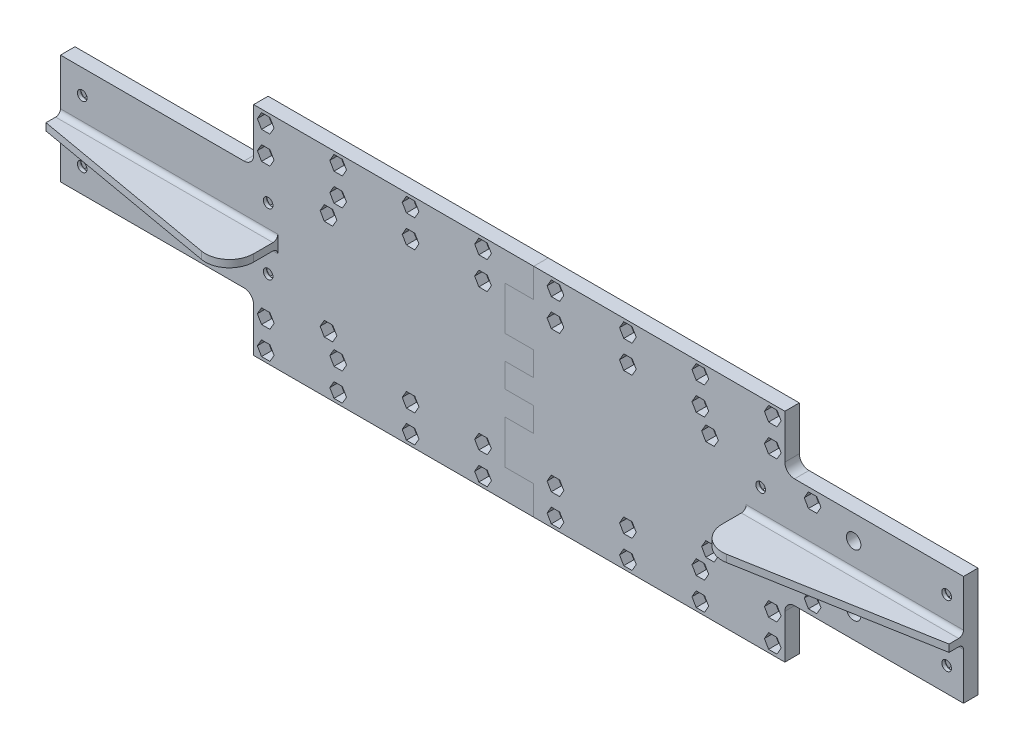
SolidWorks part; units mm, degrees
ref_plane "Top Plane" through (0, 0, 0) normal (0, 0, 1) x (1, 0, 0)
ref_plane "Right Plane" through (0, 0, 0) normal (0, 1, 0) x (1, 0, 0)
ref_plane "Front Plane" through (0, 0, 0) normal (1, 0, 0) x (0, 0, -1)
sketch "Sketch1" plane through (0, 0, 0) normal (0, 0, 1) x (1, 0, 0)
  line L0 (-187, 81) -> (187, -81) construction
  line L1 (-187, 81) -> (187, 81) construction
  line L2 (-187, 81) -> (-187, -81) construction
  line L3 (-187, -81) -> (187, -81) construction
  line L4 (187, 81) -> (187, -81) construction
  line L5 (-187, -22.75) -> (-107, -22.75) construction
  line L6 (-107, -22.75) -> (-107, -81) construction
  line L7 (113, -81) -> (113, -22.75) construction
  line L8 (113, -22.75) -> (187, -22.75) construction
  line L9 (-187, 0) -> (187, 0) construction
  line L10 (113, 22.75) -> (187, 22.75) construction
  line L11 (113, 81) -> (113, 22.75) construction
  line L12 (-107, 22.75) -> (-107, 81) construction
  line L13 (-187, 22.75) -> (-107, 22.75) construction
  line L14 (85.2, -81) -> (85.2, 81) construction
  line L15 (-93, -81) -> (-93, 81) construction
  line L16 (-187, -2.75) -> (187, -2.75) construction
  line L17 (187, 2.75) -> (-187, 2.75) construction
  text T0 "FRONT" font "Century Gothic" height in points 80
  dimension "D1" = 374
  dimension "D2" = 162
  dimension "D3" = 45.5
  dimension "D4" = 80
  dimension "D5" = 74
  dimension "D6" = 27.8
  dimension "D7" = 14
  dimension "D8" = 20
  dimension "D9" = 20
sketch "Sketch2" plane through (0, 0, 0) normal (0, 0, 1) x (1, 0, 0)
  line L0 (-187, 81) -> (-187, -81) construction
  line L1 (-187, 81) -> (187, 81) construction
  line L2 (187, 81) -> (187, -81) construction
  line L3 (-187, -81) -> (187, -81) construction
  line L4 (113, -81) -> (113, -22.75) construction
  line L5 (113, -22.75) -> (187, -22.75) construction
  line L6 (113, 22.75) -> (187, 22.75) construction
  line L7 (113, 81) -> (113, 22.75) construction
  line L8 (-107, 22.75) -> (-107, 81) construction
  line L9 (-187, 22.75) -> (-107, 22.75) construction
  line L10 (-107, -22.75) -> (-107, -81) construction
  line L11 (-187, -22.75) -> (-107, -22.75) construction
  line L12 (-187, 22.75) -> (-187, -22.75)
  line L13 (-107, 81) -> (113, 81)
  line L14 (187, 22.75) -> (187, -22.75)
  line L15 (-107, -81) -> (113, -81)
  line L16 (113, -81) -> (113, -22.75)
  line L17 (113, -22.75) -> (187, -22.75)
  line L18 (113, 22.75) -> (187, 22.75)
  line L19 (113, 81) -> (113, 22.75)
  line L20 (-107, 22.75) -> (-107, 81)
  line L21 (-187, 22.75) -> (-107, 22.75)
  line L22 (-107, -22.75) -> (-107, -81)
  line L23 (-187, -22.75) -> (-107, -22.75)
extrude "Boss-Extrude1" add sketch "Sketch2" along normal mid plane 6
sketch "Sketch5" plane through (0, 0, -3) normal (0, 0, -1) x (-1, 0, 0)
  line L0 (0, 81) -> (0, -81) construction
  line L1 (187, 81) -> (-187, 81) construction
  line L2 (187, -81) -> (-187, -81) construction
  line L4 (-180, 0) -> (178, 0) construction
  line L5 (-180, 12.75) -> (-103, 12.75) construction
  line L6 (-180, 12.75) -> (-180, -12.75) construction
  line L7 (-180, -12.75) -> (-103, -12.75) construction
  line L8 (-103, 12.75) -> (-103, -12.75) construction
  line L9 (101, 12.75) -> (178, 12.75) construction
  line L10 (101, 12.75) -> (101, -12.75) construction
  line L11 (101, -12.75) -> (178, -12.75) construction
  line L12 (178, 12.75) -> (178, -12.75) construction
  circle A8 centre (-103, -12.75) radius 2
  circle A9 centre (-103, 12.75) radius 2
  circle A10 centre (-180, 12.75) radius 2
  circle A11 centre (-180, -12.75) radius 2
  circle A12 centre (178, 12.75) radius 2
  circle A13 centre (178, -12.75) radius 2
  circle A14 centre (101, -12.75) radius 2
  circle A15 centre (101, 12.75) radius 2
  dimension "D3" = 25.5
  dimension "D6" = 4
  dimension "D1" = 77
  dimension "D2" = 103
  dimension "D4" = 101
  dimension "D5" = 77
extrude "Cut-Extrude2" cut sketch "Sketch5" against normal up to next
sketch "Sketch9" plane through (0, 0, 3) normal (0, 0, 1) x (1, 0, 0)
  line L0 (-107.9535, -35) -> (101.269, -35) construction
  line L1 (-12, -40.75) -> (18, -40.75) construction
  line L2 (-12, -29.25) -> (-42, -29.25) construction
  line L3 (-12, -29.25) -> (18, -29.25) construction
  line L4 (-194.5845, 0) -> (205.1662, 0) construction
  line L5 (3, -85.4344) -> (3, 85.4344) construction
  line L6 (-12, -40.75) -> (-42, -40.75) construction
  line L7 (-107, 81) -> (113, -81) construction
  line L8 (-40.2679, -37.75) -> (-43.7321, -37.75) construction
  line L9 (-13.7321, -37.75) -> (-15.4641, -40.75) construction
  line L10 (-15.4641, -40.75) -> (-13.7321, -43.75) construction
  line L11 (-13.7321, -43.75) -> (-10.2679, -43.75) construction
  line L12 (-10.2679, -43.75) -> (-8.5359, -40.75) construction
  line L13 (-8.5359, -40.75) -> (-10.2679, -37.75) construction
  line L14 (-10.2679, -37.75) -> (-13.7321, -37.75) construction
  line L15 (-43.7321, -37.75) -> (-45.4641, -40.75) construction
  line L16 (-45.4641, -40.75) -> (-43.7321, -43.75) construction
  line L17 (-43.7321, -43.75) -> (-40.2679, -43.75) construction
  line L18 (-40.2679, -43.75) -> (-38.5359, -40.75) construction
  line L19 (-38.5359, -40.75) -> (-40.2679, -37.75) construction
  line L20 (-70.2679, -37.75) -> (-73.7321, -37.75) construction
  line L21 (-73.7321, -37.75) -> (-75.4641, -40.75) construction
  line L22 (-75.4641, -40.75) -> (-73.7321, -43.75) construction
  line L23 (-73.7321, -43.75) -> (-70.2679, -43.75) construction
  line L24 (-70.2679, -43.75) -> (-68.5359, -40.75) construction
  line L25 (-68.5359, -40.75) -> (-70.2679, -37.75) construction
  line L26 (-100.2679, -37.75) -> (-103.7321, -37.75) construction
  line L27 (-103.7321, -37.75) -> (-105.4641, -40.75) construction
  line L28 (-105.4641, -40.75) -> (-103.7321, -43.75) construction
  line L29 (-103.7321, -43.75) -> (-100.2679, -43.75) construction
  line L30 (-100.2679, -43.75) -> (-98.5359, -40.75) construction
  line L31 (-98.5359, -40.75) -> (-100.2679, -37.75) construction
  line L32 (-43.7321, -37.75) -> (-40.2679, -43.75) construction
  line L33 (-42, -40.75) -> (-12, -40.75) construction
  line L34 (-8.5359, -29.25) -> (-10.2679, -32.25) construction
  line L35 (-10.2679, -26.25) -> (-8.5359, -29.25) construction
  line L36 (-13.7321, -26.25) -> (-10.2679, -26.25) construction
  line L37 (-15.4641, -29.25) -> (-13.7321, -26.25) construction
  line L38 (-13.7321, -32.25) -> (-15.4641, -29.25) construction
  line L39 (-10.2679, -32.25) -> (-13.7321, -32.25) construction
  line L40 (-43.7321, -26.25) -> (-40.2679, -26.25) construction
  line L41 (-45.4641, -29.25) -> (-43.7321, -26.25) construction
  line L42 (-43.7321, -32.25) -> (-45.4641, -29.25) construction
  line L43 (-40.2679, -32.25) -> (-43.7321, -32.25) construction
  line L44 (-38.5359, -29.25) -> (-40.2679, -32.25) construction
  line L45 (-40.2679, -26.25) -> (-38.5359, -29.25) construction
  line L46 (-73.7321, -26.25) -> (-70.2679, -26.25) construction
  line L47 (-75.4641, -29.25) -> (-73.7321, -26.25) construction
  line L48 (-73.7321, -32.25) -> (-75.4641, -29.25) construction
  line L49 (-70.2679, -32.25) -> (-73.7321, -32.25) construction
  line L50 (-68.5359, -29.25) -> (-70.2679, -32.25) construction
  line L51 (-70.2679, -26.25) -> (-68.5359, -29.25) construction
  line L52 (-103.7321, -26.25) -> (-100.2679, -26.25) construction
  line L53 (-105.4641, -29.25) -> (-103.7321, -26.25) construction
  line L54 (-103.7321, -32.25) -> (-105.4641, -29.25) construction
  line L55 (-100.2679, -32.25) -> (-103.7321, -32.25) construction
  line L56 (-98.5359, -29.25) -> (-100.2679, -32.25) construction
  line L57 (-100.2679, -26.25) -> (-98.5359, -29.25) construction
  line L58 (106.2679, -26.25) -> (104.5359, -29.25) construction
  line L59 (104.5359, -29.25) -> (106.2679, -32.25) construction
  line L60 (106.2679, -32.25) -> (109.7321, -32.25) construction
  line L61 (109.7321, -32.25) -> (111.4641, -29.25) construction
  line L62 (111.4641, -29.25) -> (109.7321, -26.25) construction
  line L63 (109.7321, -26.25) -> (106.2679, -26.25) construction
  line L64 (76.2679, -26.25) -> (74.5359, -29.25) construction
  line L65 (74.5359, -29.25) -> (76.2679, -32.25) construction
  line L66 (76.2679, -32.25) -> (79.7321, -32.25) construction
  line L67 (79.7321, -32.25) -> (81.4641, -29.25) construction
  line L68 (81.4641, -29.25) -> (79.7321, -26.25) construction
  line L69 (79.7321, -26.25) -> (76.2679, -26.25) construction
  line L70 (46.2679, -26.25) -> (44.5359, -29.25) construction
  line L71 (44.5359, -29.25) -> (46.2679, -32.25) construction
  line L72 (46.2679, -32.25) -> (49.7321, -32.25) construction
  line L73 (49.7321, -32.25) -> (51.4641, -29.25) construction
  line L74 (51.4641, -29.25) -> (49.7321, -26.25) construction
  line L75 (49.7321, -26.25) -> (46.2679, -26.25) construction
  line L76 (16.2679, -32.25) -> (19.7321, -32.25) construction
  line L77 (19.7321, -32.25) -> (21.4641, -29.25) construction
  line L78 (21.4641, -29.25) -> (19.7321, -26.25) construction
  line L79 (19.7321, -26.25) -> (16.2679, -26.25) construction
  line L80 (16.2679, -26.25) -> (14.5359, -29.25) construction
  line L81 (14.5359, -29.25) -> (16.2679, -32.25) construction
  line L82 (48, -40.75) -> (18, -40.75) construction
  line L83 (49.7321, -37.75) -> (46.2679, -43.75) construction
  line L84 (104.5359, -40.75) -> (106.2679, -37.75) construction
  line L85 (106.2679, -43.75) -> (104.5359, -40.75) construction
  line L86 (109.7321, -43.75) -> (106.2679, -43.75) construction
  line L87 (111.4641, -40.75) -> (109.7321, -43.75) construction
  line L88 (109.7321, -37.75) -> (111.4641, -40.75) construction
  line L89 (106.2679, -37.75) -> (109.7321, -37.75) construction
  line L90 (74.5359, -40.75) -> (76.2679, -37.75) construction
  line L91 (76.2679, -43.75) -> (74.5359, -40.75) construction
  line L92 (79.7321, -43.75) -> (76.2679, -43.75) construction
  line L93 (81.4641, -40.75) -> (79.7321, -43.75) construction
  line L94 (79.7321, -37.75) -> (81.4641, -40.75) construction
  line L95 (76.2679, -37.75) -> (79.7321, -37.75) construction
  line L96 (44.5359, -40.75) -> (46.2679, -37.75) construction
  line L97 (46.2679, -43.75) -> (44.5359, -40.75) construction
  line L98 (49.7321, -43.75) -> (46.2679, -43.75) construction
  line L99 (51.4641, -40.75) -> (49.7321, -43.75) construction
  line L100 (49.7321, -37.75) -> (51.4641, -40.75) construction
  line L101 (16.2679, -37.75) -> (19.7321, -37.75) construction
  line L102 (14.5359, -40.75) -> (16.2679, -37.75) construction
  line L103 (16.2679, -43.75) -> (14.5359, -40.75) construction
  line L104 (19.7321, -43.75) -> (16.2679, -43.75) construction
  line L105 (21.4641, -40.75) -> (19.7321, -43.75) construction
  line L106 (19.7321, -37.75) -> (21.4641, -40.75) construction
  line L107 (46.2679, -37.75) -> (49.7321, -37.75) construction
  line L108 (46.2679, 37.75) -> (49.7321, 37.75) construction
  line L109 (19.7321, 37.75) -> (21.4641, 40.75) construction
  line L110 (21.4641, 40.75) -> (19.7321, 43.75) construction
  line L111 (19.7321, 43.75) -> (16.2679, 43.75) construction
  line L112 (16.2679, 43.75) -> (14.5359, 40.75) construction
  line L113 (14.5359, 40.75) -> (16.2679, 37.75) construction
  line L114 (16.2679, 37.75) -> (19.7321, 37.75) construction
  line L115 (49.7321, 37.75) -> (51.4641, 40.75) construction
  line L116 (51.4641, 40.75) -> (49.7321, 43.75) construction
  line L117 (49.7321, 43.75) -> (46.2679, 43.75) construction
  line L118 (46.2679, 43.75) -> (44.5359, 40.75) construction
  line L119 (44.5359, 40.75) -> (46.2679, 37.75) construction
  line L120 (76.2679, 37.75) -> (79.7321, 37.75) construction
  line L121 (79.7321, 37.75) -> (81.4641, 40.75) construction
  line L122 (81.4641, 40.75) -> (79.7321, 43.75) construction
  line L123 (79.7321, 43.75) -> (76.2679, 43.75) construction
  line L124 (76.2679, 43.75) -> (74.5359, 40.75) construction
  line L125 (74.5359, 40.75) -> (76.2679, 37.75) construction
  line L126 (106.2679, 37.75) -> (109.7321, 37.75) construction
  line L127 (109.7321, 37.75) -> (111.4641, 40.75) construction
  line L128 (111.4641, 40.75) -> (109.7321, 43.75) construction
  line L129 (109.7321, 43.75) -> (106.2679, 43.75) construction
  line L130 (106.2679, 43.75) -> (104.5359, 40.75) construction
  line L131 (104.5359, 40.75) -> (106.2679, 37.75) construction
  line L132 (49.7321, 37.75) -> (46.2679, 43.75) construction
  line L133 (48, 40.75) -> (18, 40.75) construction
  line L134 (14.5359, 29.25) -> (16.2679, 32.25) construction
  line L135 (16.2679, 26.25) -> (14.5359, 29.25) construction
  line L136 (19.7321, 26.25) -> (16.2679, 26.25) construction
  line L137 (21.4641, 29.25) -> (19.7321, 26.25) construction
  line L138 (19.7321, 32.25) -> (21.4641, 29.25) construction
  line L139 (16.2679, 32.25) -> (19.7321, 32.25) construction
  line L140 (49.7321, 26.25) -> (46.2679, 26.25) construction
  line L141 (51.4641, 29.25) -> (49.7321, 26.25) construction
  line L142 (49.7321, 32.25) -> (51.4641, 29.25) construction
  line L143 (46.2679, 32.25) -> (49.7321, 32.25) construction
  line L144 (44.5359, 29.25) -> (46.2679, 32.25) construction
  line L145 (46.2679, 26.25) -> (44.5359, 29.25) construction
  line L146 (79.7321, 26.25) -> (76.2679, 26.25) construction
  line L147 (81.4641, 29.25) -> (79.7321, 26.25) construction
  line L148 (79.7321, 32.25) -> (81.4641, 29.25) construction
  line L149 (76.2679, 32.25) -> (79.7321, 32.25) construction
  line L150 (74.5359, 29.25) -> (76.2679, 32.25) construction
  line L151 (76.2679, 26.25) -> (74.5359, 29.25) construction
  line L152 (109.7321, 26.25) -> (106.2679, 26.25) construction
  line L153 (111.4641, 29.25) -> (109.7321, 26.25) construction
  line L154 (109.7321, 32.25) -> (111.4641, 29.25) construction
  line L155 (106.2679, 32.25) -> (109.7321, 32.25) construction
  line L156 (104.5359, 29.25) -> (106.2679, 32.25) construction
  line L157 (106.2679, 26.25) -> (104.5359, 29.25) construction
  line L158 (-100.2679, 26.25) -> (-98.5359, 29.25) construction
  line L159 (-98.5359, 29.25) -> (-100.2679, 32.25) construction
  line L160 (-100.2679, 32.25) -> (-103.7321, 32.25) construction
  line L161 (-103.7321, 32.25) -> (-105.4641, 29.25) construction
  line L162 (-105.4641, 29.25) -> (-103.7321, 26.25) construction
  line L163 (-103.7321, 26.25) -> (-100.2679, 26.25) construction
  line L164 (-70.2679, 26.25) -> (-68.5359, 29.25) construction
  line L165 (-68.5359, 29.25) -> (-70.2679, 32.25) construction
  line L166 (-70.2679, 32.25) -> (-73.7321, 32.25) construction
  line L167 (-73.7321, 32.25) -> (-75.4641, 29.25) construction
  line L168 (-75.4641, 29.25) -> (-73.7321, 26.25) construction
  line L169 (-73.7321, 26.25) -> (-70.2679, 26.25) construction
  line L170 (-40.2679, 26.25) -> (-38.5359, 29.25) construction
  line L171 (-38.5359, 29.25) -> (-40.2679, 32.25) construction
  line L172 (-40.2679, 32.25) -> (-43.7321, 32.25) construction
  line L173 (-43.7321, 32.25) -> (-45.4641, 29.25) construction
  line L174 (-45.4641, 29.25) -> (-43.7321, 26.25) construction
  line L175 (-43.7321, 26.25) -> (-40.2679, 26.25) construction
  line L176 (-10.2679, 32.25) -> (-13.7321, 32.25) construction
  line L177 (-13.7321, 32.25) -> (-15.4641, 29.25) construction
  line L178 (-15.4641, 29.25) -> (-13.7321, 26.25) construction
  line L179 (-13.7321, 26.25) -> (-10.2679, 26.25) construction
  line L180 (-10.2679, 26.25) -> (-8.5359, 29.25) construction
  line L181 (-8.5359, 29.25) -> (-10.2679, 32.25) construction
  line L182 (-42, 40.75) -> (-12, 40.75) construction
  line L183 (-43.7321, 37.75) -> (-40.2679, 43.75) construction
  line L184 (-98.5359, 40.75) -> (-100.2679, 37.75) construction
  line L185 (-100.2679, 43.75) -> (-98.5359, 40.75) construction
  line L186 (-103.7321, 43.75) -> (-100.2679, 43.75) construction
  line L187 (-105.4641, 40.75) -> (-103.7321, 43.75) construction
  line L188 (-103.7321, 37.75) -> (-105.4641, 40.75) construction
  line L189 (-100.2679, 37.75) -> (-103.7321, 37.75) construction
  line L190 (-68.5359, 40.75) -> (-70.2679, 37.75) construction
  line L191 (-70.2679, 43.75) -> (-68.5359, 40.75) construction
  line L192 (-73.7321, 43.75) -> (-70.2679, 43.75) construction
  line L193 (-75.4641, 40.75) -> (-73.7321, 43.75) construction
  line L194 (-73.7321, 37.75) -> (-75.4641, 40.75) construction
  line L195 (-70.2679, 37.75) -> (-73.7321, 37.75) construction
  line L196 (-38.5359, 40.75) -> (-40.2679, 37.75) construction
  line L197 (-40.2679, 43.75) -> (-38.5359, 40.75) construction
  line L198 (-43.7321, 43.75) -> (-40.2679, 43.75) construction
  line L199 (-45.4641, 40.75) -> (-43.7321, 43.75) construction
  line L200 (-43.7321, 37.75) -> (-45.4641, 40.75) construction
  line L201 (-10.2679, 37.75) -> (-13.7321, 37.75) construction
  line L202 (-8.5359, 40.75) -> (-10.2679, 37.75) construction
  line L203 (-10.2679, 43.75) -> (-8.5359, 40.75) construction
  line L204 (-13.7321, 43.75) -> (-10.2679, 43.75) construction
  line L205 (-15.4641, 40.75) -> (-13.7321, 43.75) construction
  line L206 (-13.7321, 37.75) -> (-15.4641, 40.75) construction
  line L207 (-40.2679, 37.75) -> (-43.7321, 37.75) construction
  line L208 (-12, 40.75) -> (-42, 40.75) construction
  line L209 (-12, 29.25) -> (18, 29.25) construction
  line L210 (-12, 29.25) -> (-42, 29.25) construction
  line L211 (-12, 40.75) -> (18, 40.75) construction
  line L212 (-107.9535, 35) -> (101.269, 35) construction
  circle A0 centre (-12, -40.75) radius 1.75
  circle A1 centre (-42, -40.75) radius 1.75
  circle A2 centre (-72, -40.75) radius 1.75
  circle A3 centre (-102, -40.75) radius 1.75
  circle A4 centre (108, -40.75) radius 1.75
  circle A5 centre (78, -40.75) radius 1.75
  circle A6 centre (48, -40.75) radius 1.75
  circle A7 centre (18, -40.75) radius 1.75
  circle A8 centre (18, -29.25) radius 1.75
  circle A9 centre (48, -29.25) radius 1.75
  circle A10 centre (78, -29.25) radius 1.75
  circle A11 centre (108, -29.25) radius 1.75
  circle A12 centre (-102, -29.25) radius 1.75
  circle A13 centre (-72, -29.25) radius 1.75
  circle A14 centre (-42, -29.25) radius 1.75
  circle A15 centre (-12, -29.25) radius 1.75
  circle A16 centre (-12, -40.75) radius 3 construction
  circle A17 centre (-12, 40.75) radius 3 construction
  circle A18 centre (-12, 29.25) radius 1.75
  circle A19 centre (-42, 29.25) radius 1.75
  circle A20 centre (-72, 29.25) radius 1.75
  circle A21 centre (-102, 29.25) radius 1.75
  circle A22 centre (108, 29.25) radius 1.75
  circle A23 centre (78, 29.25) radius 1.75
  circle A24 centre (48, 29.25) radius 1.75
  circle A25 centre (18, 29.25) radius 1.75
  circle A26 centre (18, 40.75) radius 1.75
  circle A27 centre (48, 40.75) radius 1.75
  circle A28 centre (78, 40.75) radius 1.75
  circle A29 centre (108, 40.75) radius 1.75
  circle A30 centre (-102, 40.75) radius 1.75
  circle A31 centre (-72, 40.75) radius 1.75
  circle A32 centre (-42, 40.75) radius 1.75
  circle A33 centre (-12, 40.75) radius 1.75
  point P6 (3, -40.75)
  point P39 (3, -29.25)
  point P46 (3, 0)
  point P277 (3, 29.25)
  point P278 (3, 40.75)
  dimension "D3" = 3.5
  dimension "D1" = 11.5
  dimension "D2" = 35
  dimension "D5" = 30
  dimension "D6" = 6
  dimension "D4" = 4
  dimension "D7" = 4
extrude "Cut-Extrude6" cut sketch "Sketch9" against normal through all
sketch "Sketch10" plane through (0, 0, 3) normal (0, 0, 1) x (1, 0, 0)
  line L0 (-103.7321, -43.75) -> (-100.2679, -43.75) construction
  line L1 (-105.4641, -40.75) -> (-103.7321, -43.75) construction
  line L2 (-103.7321, -37.75) -> (-105.4641, -40.75) construction
  line L3 (-100.2679, -37.75) -> (-103.7321, -37.75) construction
  line L4 (-98.5359, -40.75) -> (-100.2679, -37.75) construction
  line L5 (-100.2679, -43.75) -> (-98.5359, -40.75) construction
  line L6 (-103.7321, -43.75) -> (-100.2679, -43.75)
  line L7 (-105.4641, -40.75) -> (-103.7321, -43.75)
  line L8 (-103.7321, -37.75) -> (-105.4641, -40.75)
  line L9 (-100.2679, -37.75) -> (-103.7321, -37.75)
  line L10 (-98.5359, -40.75) -> (-100.2679, -37.75)
  line L11 (-100.2679, -43.75) -> (-98.5359, -40.75)
  line L12 (-73.7321, -43.75) -> (-70.2679, -43.75) construction
  line L13 (-75.4641, -40.75) -> (-73.7321, -43.75) construction
  line L14 (-73.7321, -37.75) -> (-75.4641, -40.75) construction
  line L15 (-70.2679, -37.75) -> (-73.7321, -37.75) construction
  line L16 (-68.5359, -40.75) -> (-70.2679, -37.75) construction
  line L17 (-70.2679, -43.75) -> (-68.5359, -40.75) construction
  line L18 (-73.7321, -43.75) -> (-70.2679, -43.75)
  line L19 (-75.4641, -40.75) -> (-73.7321, -43.75)
  line L20 (-73.7321, -37.75) -> (-75.4641, -40.75)
  line L21 (-70.2679, -37.75) -> (-73.7321, -37.75)
  line L22 (-68.5359, -40.75) -> (-70.2679, -37.75)
  line L23 (-70.2679, -43.75) -> (-68.5359, -40.75)
  line L24 (-43.7321, -43.75) -> (-40.2679, -43.75) construction
  line L25 (-45.4641, -40.75) -> (-43.7321, -43.75) construction
  line L26 (-43.7321, -37.75) -> (-45.4641, -40.75) construction
  line L27 (-40.2679, -37.75) -> (-43.7321, -37.75) construction
  line L28 (-38.5359, -40.75) -> (-40.2679, -37.75) construction
  line L29 (-40.2679, -43.75) -> (-38.5359, -40.75) construction
  line L30 (-43.7321, -43.75) -> (-40.2679, -43.75)
  line L31 (-45.4641, -40.75) -> (-43.7321, -43.75)
  line L32 (-43.7321, -37.75) -> (-45.4641, -40.75)
  line L33 (-40.2679, -37.75) -> (-43.7321, -37.75)
  line L34 (-38.5359, -40.75) -> (-40.2679, -37.75)
  line L35 (-40.2679, -43.75) -> (-38.5359, -40.75)
  line L36 (-13.7321, -43.75) -> (-10.2679, -43.75) construction
  line L37 (-15.4641, -40.75) -> (-13.7321, -43.75) construction
  line L38 (-13.7321, -37.75) -> (-15.4641, -40.75) construction
  line L39 (-10.2679, -37.75) -> (-13.7321, -37.75) construction
  line L40 (-8.5359, -40.75) -> (-10.2679, -37.75) construction
  line L41 (-10.2679, -43.75) -> (-8.5359, -40.75) construction
  line L42 (-13.7321, -43.75) -> (-10.2679, -43.75)
  line L43 (-15.4641, -40.75) -> (-13.7321, -43.75)
  line L44 (-13.7321, -37.75) -> (-15.4641, -40.75)
  line L45 (-10.2679, -37.75) -> (-13.7321, -37.75)
  line L46 (-8.5359, -40.75) -> (-10.2679, -37.75)
  line L47 (-10.2679, -43.75) -> (-8.5359, -40.75)
  line L48 (79.7321, -43.75) -> (76.2679, -43.75) construction
  line L49 (81.4641, -40.75) -> (79.7321, -43.75) construction
  line L50 (79.7321, -37.75) -> (81.4641, -40.75) construction
  line L51 (76.2679, -37.75) -> (79.7321, -37.75) construction
  line L52 (74.5359, -40.75) -> (76.2679, -37.75) construction
  line L53 (76.2679, -43.75) -> (74.5359, -40.75) construction
  line L54 (46.2679, -37.75) -> (49.7321, -37.75) construction
  line L55 (44.5359, -40.75) -> (46.2679, -37.75) construction
  line L56 (46.2679, -43.75) -> (44.5359, -40.75) construction
  line L57 (16.2679, -43.75) -> (14.5359, -40.75) construction
  line L58 (19.7321, -43.75) -> (16.2679, -43.75) construction
  line L59 (21.4641, -40.75) -> (19.7321, -43.75) construction
  line L60 (19.7321, -37.75) -> (21.4641, -40.75) construction
  line L61 (16.2679, -37.75) -> (19.7321, -37.75) construction
  line L62 (14.5359, -40.75) -> (16.2679, -37.75) construction
  line L63 (79.7321, -43.75) -> (76.2679, -43.75)
  line L64 (81.4641, -40.75) -> (79.7321, -43.75)
  line L65 (79.7321, -37.75) -> (81.4641, -40.75)
  line L66 (76.2679, -37.75) -> (79.7321, -37.75)
  line L67 (74.5359, -40.75) -> (76.2679, -37.75)
  line L68 (76.2679, -43.75) -> (74.5359, -40.75)
  line L69 (46.2679, -37.75) -> (49.7321, -37.75)
  line L70 (44.5359, -40.75) -> (46.2679, -37.75)
  line L71 (46.2679, -43.75) -> (44.5359, -40.75)
  line L72 (16.2679, -43.75) -> (14.5359, -40.75)
  line L73 (19.7321, -43.75) -> (16.2679, -43.75)
  line L74 (21.4641, -40.75) -> (19.7321, -43.75)
  line L75 (19.7321, -37.75) -> (21.4641, -40.75)
  line L76 (16.2679, -37.75) -> (19.7321, -37.75)
  line L77 (14.5359, -40.75) -> (16.2679, -37.75)
  line L78 (49.7321, -43.75) -> (46.2679, -43.75) construction
  line L79 (51.4641, -40.75) -> (49.7321, -43.75) construction
  line L80 (49.7321, -37.75) -> (51.4641, -40.75) construction
  line L81 (49.7321, -43.75) -> (46.2679, -43.75)
  line L82 (51.4641, -40.75) -> (49.7321, -43.75)
  line L83 (49.7321, -37.75) -> (51.4641, -40.75)
  line L84 (46.2679, -32.25) -> (49.7321, -32.25) construction
  line L85 (44.5359, -29.25) -> (46.2679, -32.25) construction
  line L86 (46.2679, -26.25) -> (44.5359, -29.25) construction
  line L87 (49.7321, -26.25) -> (46.2679, -26.25) construction
  line L88 (51.4641, -29.25) -> (49.7321, -26.25) construction
  line L89 (49.7321, -32.25) -> (51.4641, -29.25) construction
  line L90 (79.7321, -32.25) -> (81.4641, -29.25) construction
  line L91 (76.2679, -32.25) -> (79.7321, -32.25) construction
  line L92 (74.5359, -29.25) -> (76.2679, -32.25) construction
  line L93 (76.2679, -26.25) -> (74.5359, -29.25) construction
  line L94 (79.7321, -26.25) -> (76.2679, -26.25) construction
  line L95 (81.4641, -29.25) -> (79.7321, -26.25) construction
  line L96 (106.2679, -26.25) -> (104.5359, -29.25) construction
  line L97 (109.7321, -26.25) -> (106.2679, -26.25) construction
  line L98 (111.4641, -29.25) -> (109.7321, -26.25) construction
  line L99 (109.7321, -32.25) -> (111.4641, -29.25) construction
  line L100 (106.2679, -32.25) -> (109.7321, -32.25) construction
  line L101 (104.5359, -29.25) -> (106.2679, -32.25) construction
  line L102 (106.2679, -43.75) -> (104.5359, -40.75) construction
  line L103 (109.7321, -43.75) -> (106.2679, -43.75) construction
  line L104 (111.4641, -40.75) -> (109.7321, -43.75) construction
  line L105 (109.7321, -37.75) -> (111.4641, -40.75) construction
  line L106 (106.2679, -37.75) -> (109.7321, -37.75) construction
  line L107 (104.5359, -40.75) -> (106.2679, -37.75) construction
  line L108 (46.2679, -32.25) -> (49.7321, -32.25)
  line L109 (44.5359, -29.25) -> (46.2679, -32.25)
  line L110 (46.2679, -26.25) -> (44.5359, -29.25)
  line L111 (49.7321, -26.25) -> (46.2679, -26.25)
  line L112 (51.4641, -29.25) -> (49.7321, -26.25)
  line L113 (49.7321, -32.25) -> (51.4641, -29.25)
  line L114 (79.7321, -32.25) -> (81.4641, -29.25)
  line L115 (76.2679, -32.25) -> (79.7321, -32.25)
  line L116 (74.5359, -29.25) -> (76.2679, -32.25)
  line L117 (76.2679, -26.25) -> (74.5359, -29.25)
  line L118 (79.7321, -26.25) -> (76.2679, -26.25)
  line L119 (81.4641, -29.25) -> (79.7321, -26.25)
  line L120 (106.2679, -26.25) -> (104.5359, -29.25)
  line L121 (109.7321, -26.25) -> (106.2679, -26.25)
  line L122 (111.4641, -29.25) -> (109.7321, -26.25)
  line L123 (109.7321, -32.25) -> (111.4641, -29.25)
  line L124 (106.2679, -32.25) -> (109.7321, -32.25)
  line L125 (104.5359, -29.25) -> (106.2679, -32.25)
  line L126 (106.2679, -43.75) -> (104.5359, -40.75)
  line L127 (109.7321, -43.75) -> (106.2679, -43.75)
  line L128 (111.4641, -40.75) -> (109.7321, -43.75)
  line L129 (109.7321, -37.75) -> (111.4641, -40.75)
  line L130 (106.2679, -37.75) -> (109.7321, -37.75)
  line L131 (104.5359, -40.75) -> (106.2679, -37.75)
  line L132 (-43.7321, -32.25) -> (-45.4641, -29.25) construction
  line L133 (-40.2679, -32.25) -> (-43.7321, -32.25) construction
  line L134 (-38.5359, -29.25) -> (-40.2679, -32.25) construction
  line L135 (-40.2679, -26.25) -> (-38.5359, -29.25) construction
  line L136 (-43.7321, -26.25) -> (-40.2679, -26.25) construction
  line L137 (-45.4641, -29.25) -> (-43.7321, -26.25) construction
  line L138 (-13.7321, -32.25) -> (-15.4641, -29.25) construction
  line L139 (-10.2679, -32.25) -> (-13.7321, -32.25) construction
  line L140 (-8.5359, -29.25) -> (-10.2679, -32.25) construction
  line L141 (-10.2679, -26.25) -> (-8.5359, -29.25) construction
  line L142 (-13.7321, -26.25) -> (-10.2679, -26.25) construction
  line L143 (-15.4641, -29.25) -> (-13.7321, -26.25) construction
  line L144 (19.7321, -32.25) -> (21.4641, -29.25) construction
  line L145 (16.2679, -32.25) -> (19.7321, -32.25) construction
  line L146 (14.5359, -29.25) -> (16.2679, -32.25) construction
  line L147 (16.2679, -26.25) -> (14.5359, -29.25) construction
  line L148 (19.7321, -26.25) -> (16.2679, -26.25) construction
  line L149 (21.4641, -29.25) -> (19.7321, -26.25) construction
  line L150 (-43.7321, -32.25) -> (-45.4641, -29.25)
  line L151 (-40.2679, -32.25) -> (-43.7321, -32.25)
  line L152 (-38.5359, -29.25) -> (-40.2679, -32.25)
  line L153 (-40.2679, -26.25) -> (-38.5359, -29.25)
  line L154 (-43.7321, -26.25) -> (-40.2679, -26.25)
  line L155 (-45.4641, -29.25) -> (-43.7321, -26.25)
  line L156 (-13.7321, -32.25) -> (-15.4641, -29.25)
  line L157 (-10.2679, -32.25) -> (-13.7321, -32.25)
  line L158 (-8.5359, -29.25) -> (-10.2679, -32.25)
  line L159 (-10.2679, -26.25) -> (-8.5359, -29.25)
  line L160 (-13.7321, -26.25) -> (-10.2679, -26.25)
  line L161 (-15.4641, -29.25) -> (-13.7321, -26.25)
  line L162 (19.7321, -32.25) -> (21.4641, -29.25)
  line L163 (16.2679, -32.25) -> (19.7321, -32.25)
  line L164 (14.5359, -29.25) -> (16.2679, -32.25)
  line L165 (16.2679, -26.25) -> (14.5359, -29.25)
  line L166 (19.7321, -26.25) -> (16.2679, -26.25)
  line L167 (21.4641, -29.25) -> (19.7321, -26.25)
  line L168 (-100.2679, -32.25) -> (-103.7321, -32.25) construction
  line L169 (-98.5359, -29.25) -> (-100.2679, -32.25) construction
  line L170 (-100.2679, -26.25) -> (-98.5359, -29.25) construction
  line L171 (-103.7321, -26.25) -> (-100.2679, -26.25) construction
  line L172 (-105.4641, -29.25) -> (-103.7321, -26.25) construction
  line L173 (-103.7321, -32.25) -> (-105.4641, -29.25) construction
  line L174 (-68.5359, -29.25) -> (-70.2679, -32.25) construction
  line L175 (-70.2679, -26.25) -> (-68.5359, -29.25) construction
  line L176 (-73.7321, -26.25) -> (-70.2679, -26.25) construction
  line L177 (-75.4641, -29.25) -> (-73.7321, -26.25) construction
  line L178 (-73.7321, -32.25) -> (-75.4641, -29.25) construction
  line L179 (-70.2679, -32.25) -> (-73.7321, -32.25) construction
  line L180 (-100.2679, -32.25) -> (-103.7321, -32.25)
  line L181 (-98.5359, -29.25) -> (-100.2679, -32.25)
  line L182 (-100.2679, -26.25) -> (-98.5359, -29.25)
  line L183 (-103.7321, -26.25) -> (-100.2679, -26.25)
  line L184 (-105.4641, -29.25) -> (-103.7321, -26.25)
  line L185 (-103.7321, -32.25) -> (-105.4641, -29.25)
  line L186 (-68.5359, -29.25) -> (-70.2679, -32.25)
  line L187 (-70.2679, -26.25) -> (-68.5359, -29.25)
  line L188 (-73.7321, -26.25) -> (-70.2679, -26.25)
  line L189 (-75.4641, -29.25) -> (-73.7321, -26.25)
  line L190 (-73.7321, -32.25) -> (-75.4641, -29.25)
  line L191 (-70.2679, -32.25) -> (-73.7321, -32.25)
  line L192 (-73.7321, 26.25) -> (-70.2679, 26.25) construction
  line L193 (-75.4641, 29.25) -> (-73.7321, 26.25) construction
  line L194 (-73.7321, 32.25) -> (-75.4641, 29.25) construction
  line L195 (-70.2679, 32.25) -> (-73.7321, 32.25) construction
  line L196 (-68.5359, 29.25) -> (-70.2679, 32.25) construction
  line L197 (-70.2679, 26.25) -> (-68.5359, 29.25) construction
  line L198 (-73.7321, 37.75) -> (-75.4641, 40.75) construction
  line L199 (-70.2679, 37.75) -> (-73.7321, 37.75) construction
  line L200 (-68.5359, 40.75) -> (-70.2679, 37.75) construction
  line L201 (-70.2679, 43.75) -> (-68.5359, 40.75) construction
  line L202 (-73.7321, 43.75) -> (-70.2679, 43.75) construction
  line L203 (-75.4641, 40.75) -> (-73.7321, 43.75) construction
  line L204 (-103.7321, 26.25) -> (-100.2679, 26.25) construction
  line L205 (-105.4641, 29.25) -> (-103.7321, 26.25) construction
  line L206 (-103.7321, 32.25) -> (-105.4641, 29.25) construction
  line L207 (-100.2679, 32.25) -> (-103.7321, 32.25) construction
  line L208 (-98.5359, 29.25) -> (-100.2679, 32.25) construction
  line L209 (-100.2679, 26.25) -> (-98.5359, 29.25) construction
  line L210 (-103.7321, 37.75) -> (-105.4641, 40.75) construction
  line L211 (-100.2679, 37.75) -> (-103.7321, 37.75) construction
  line L212 (-98.5359, 40.75) -> (-100.2679, 37.75) construction
  line L213 (-100.2679, 43.75) -> (-98.5359, 40.75) construction
  line L214 (-103.7321, 43.75) -> (-100.2679, 43.75) construction
  line L215 (-105.4641, 40.75) -> (-103.7321, 43.75) construction
  line L216 (-73.7321, 26.25) -> (-70.2679, 26.25)
  line L217 (-75.4641, 29.25) -> (-73.7321, 26.25)
  line L218 (-73.7321, 32.25) -> (-75.4641, 29.25)
  line L219 (-70.2679, 32.25) -> (-73.7321, 32.25)
  line L220 (-68.5359, 29.25) -> (-70.2679, 32.25)
  line L221 (-70.2679, 26.25) -> (-68.5359, 29.25)
  line L222 (-73.7321, 37.75) -> (-75.4641, 40.75)
  line L223 (-70.2679, 37.75) -> (-73.7321, 37.75)
  line L224 (-68.5359, 40.75) -> (-70.2679, 37.75)
  line L225 (-70.2679, 43.75) -> (-68.5359, 40.75)
  line L226 (-73.7321, 43.75) -> (-70.2679, 43.75)
  line L227 (-75.4641, 40.75) -> (-73.7321, 43.75)
  line L228 (-103.7321, 26.25) -> (-100.2679, 26.25)
  line L229 (-105.4641, 29.25) -> (-103.7321, 26.25)
  line L230 (-103.7321, 32.25) -> (-105.4641, 29.25)
  line L231 (-100.2679, 32.25) -> (-103.7321, 32.25)
  line L232 (-98.5359, 29.25) -> (-100.2679, 32.25)
  line L233 (-100.2679, 26.25) -> (-98.5359, 29.25)
  line L234 (-103.7321, 37.75) -> (-105.4641, 40.75)
  line L235 (-100.2679, 37.75) -> (-103.7321, 37.75)
  line L236 (-98.5359, 40.75) -> (-100.2679, 37.75)
  line L237 (-100.2679, 43.75) -> (-98.5359, 40.75)
  line L238 (-103.7321, 43.75) -> (-100.2679, 43.75)
  line L239 (-105.4641, 40.75) -> (-103.7321, 43.75)
  line L240 (-15.4641, 29.25) -> (-13.7321, 26.25) construction
  line L241 (-13.7321, 32.25) -> (-15.4641, 29.25) construction
  line L242 (-10.2679, 32.25) -> (-13.7321, 32.25) construction
  line L243 (-8.5359, 29.25) -> (-10.2679, 32.25) construction
  line L244 (-10.2679, 26.25) -> (-8.5359, 29.25) construction
  line L245 (-13.7321, 26.25) -> (-10.2679, 26.25) construction
  line L246 (-13.7321, 37.75) -> (-15.4641, 40.75) construction
  line L247 (-10.2679, 37.75) -> (-13.7321, 37.75) construction
  line L248 (-8.5359, 40.75) -> (-10.2679, 37.75) construction
  line L249 (-10.2679, 43.75) -> (-8.5359, 40.75) construction
  line L250 (-13.7321, 43.75) -> (-10.2679, 43.75) construction
  line L251 (-15.4641, 40.75) -> (-13.7321, 43.75) construction
  line L252 (-43.7321, 26.25) -> (-40.2679, 26.25) construction
  line L253 (-45.4641, 29.25) -> (-43.7321, 26.25) construction
  line L254 (-43.7321, 32.25) -> (-45.4641, 29.25) construction
  line L255 (-40.2679, 32.25) -> (-43.7321, 32.25) construction
  line L256 (-38.5359, 29.25) -> (-40.2679, 32.25) construction
  line L257 (-40.2679, 26.25) -> (-38.5359, 29.25) construction
  line L258 (-40.2679, 37.75) -> (-43.7321, 37.75) construction
  line L259 (-38.5359, 40.75) -> (-40.2679, 37.75) construction
  line L260 (-40.2679, 43.75) -> (-38.5359, 40.75) construction
  line L261 (-43.7321, 43.75) -> (-40.2679, 43.75) construction
  line L262 (-45.4641, 40.75) -> (-43.7321, 43.75) construction
  line L263 (-43.7321, 37.75) -> (-45.4641, 40.75) construction
  line L264 (-15.4641, 29.25) -> (-13.7321, 26.25)
  line L265 (-13.7321, 32.25) -> (-15.4641, 29.25)
  line L266 (-10.2679, 32.25) -> (-13.7321, 32.25)
  line L267 (-8.5359, 29.25) -> (-10.2679, 32.25)
  line L268 (-10.2679, 26.25) -> (-8.5359, 29.25)
  line L269 (-13.7321, 26.25) -> (-10.2679, 26.25)
  line L270 (-13.7321, 37.75) -> (-15.4641, 40.75)
  line L271 (-10.2679, 37.75) -> (-13.7321, 37.75)
  line L272 (-8.5359, 40.75) -> (-10.2679, 37.75)
  line L273 (-10.2679, 43.75) -> (-8.5359, 40.75)
  line L274 (-13.7321, 43.75) -> (-10.2679, 43.75)
  line L275 (-15.4641, 40.75) -> (-13.7321, 43.75)
  line L276 (-43.7321, 26.25) -> (-40.2679, 26.25)
  line L277 (-45.4641, 29.25) -> (-43.7321, 26.25)
  line L278 (-43.7321, 32.25) -> (-45.4641, 29.25)
  line L279 (-40.2679, 32.25) -> (-43.7321, 32.25)
  line L280 (-38.5359, 29.25) -> (-40.2679, 32.25)
  line L281 (-40.2679, 26.25) -> (-38.5359, 29.25)
  line L282 (-40.2679, 37.75) -> (-43.7321, 37.75)
  line L283 (-38.5359, 40.75) -> (-40.2679, 37.75)
  line L284 (-40.2679, 43.75) -> (-38.5359, 40.75)
  line L285 (-43.7321, 43.75) -> (-40.2679, 43.75)
  line L286 (-45.4641, 40.75) -> (-43.7321, 43.75)
  line L287 (-43.7321, 37.75) -> (-45.4641, 40.75)
  line L288 (46.2679, 26.25) -> (44.5359, 29.25) construction
  line L289 (49.7321, 26.25) -> (46.2679, 26.25) construction
  line L290 (51.4641, 29.25) -> (49.7321, 26.25) construction
  line L291 (49.7321, 32.25) -> (51.4641, 29.25) construction
  line L292 (46.2679, 32.25) -> (49.7321, 32.25) construction
  line L293 (44.5359, 29.25) -> (46.2679, 32.25) construction
  line L294 (46.2679, 37.75) -> (49.7321, 37.75) construction
  line L295 (44.5359, 40.75) -> (46.2679, 37.75) construction
  line L296 (46.2679, 43.75) -> (44.5359, 40.75) construction
  line L297 (49.7321, 43.75) -> (46.2679, 43.75) construction
  line L298 (51.4641, 40.75) -> (49.7321, 43.75) construction
  line L299 (49.7321, 37.75) -> (51.4641, 40.75) construction
  line L300 (16.2679, 26.25) -> (14.5359, 29.25) construction
  line L301 (19.7321, 26.25) -> (16.2679, 26.25) construction
  line L302 (21.4641, 29.25) -> (19.7321, 26.25) construction
  line L303 (19.7321, 32.25) -> (21.4641, 29.25) construction
  line L304 (16.2679, 32.25) -> (19.7321, 32.25) construction
  line L305 (14.5359, 29.25) -> (16.2679, 32.25) construction
  line L306 (16.2679, 37.75) -> (19.7321, 37.75) construction
  line L307 (14.5359, 40.75) -> (16.2679, 37.75) construction
  line L308 (16.2679, 43.75) -> (14.5359, 40.75) construction
  line L309 (19.7321, 43.75) -> (16.2679, 43.75) construction
  line L310 (21.4641, 40.75) -> (19.7321, 43.75) construction
  line L311 (19.7321, 37.75) -> (21.4641, 40.75) construction
  line L312 (46.2679, 26.25) -> (44.5359, 29.25)
  line L313 (49.7321, 26.25) -> (46.2679, 26.25)
  line L314 (51.4641, 29.25) -> (49.7321, 26.25)
  line L315 (49.7321, 32.25) -> (51.4641, 29.25)
  line L316 (46.2679, 32.25) -> (49.7321, 32.25)
  line L317 (44.5359, 29.25) -> (46.2679, 32.25)
  line L318 (46.2679, 37.75) -> (49.7321, 37.75)
  line L319 (44.5359, 40.75) -> (46.2679, 37.75)
  line L320 (46.2679, 43.75) -> (44.5359, 40.75)
  line L321 (49.7321, 43.75) -> (46.2679, 43.75)
  line L322 (51.4641, 40.75) -> (49.7321, 43.75)
  line L323 (49.7321, 37.75) -> (51.4641, 40.75)
  line L324 (16.2679, 26.25) -> (14.5359, 29.25)
  line L325 (19.7321, 26.25) -> (16.2679, 26.25)
  line L326 (21.4641, 29.25) -> (19.7321, 26.25)
  line L327 (19.7321, 32.25) -> (21.4641, 29.25)
  line L328 (16.2679, 32.25) -> (19.7321, 32.25)
  line L329 (14.5359, 29.25) -> (16.2679, 32.25)
  line L330 (16.2679, 37.75) -> (19.7321, 37.75)
  line L331 (14.5359, 40.75) -> (16.2679, 37.75)
  line L332 (16.2679, 43.75) -> (14.5359, 40.75)
  line L333 (19.7321, 43.75) -> (16.2679, 43.75)
  line L334 (21.4641, 40.75) -> (19.7321, 43.75)
  line L335 (19.7321, 37.75) -> (21.4641, 40.75)
  line L336 (106.2679, 26.25) -> (104.5359, 29.25) construction
  line L337 (109.7321, 26.25) -> (106.2679, 26.25) construction
  line L338 (111.4641, 29.25) -> (109.7321, 26.25) construction
  line L339 (109.7321, 32.25) -> (111.4641, 29.25) construction
  line L340 (106.2679, 32.25) -> (109.7321, 32.25) construction
  line L341 (104.5359, 29.25) -> (106.2679, 32.25) construction
  line L342 (106.2679, 37.75) -> (109.7321, 37.75) construction
  line L343 (104.5359, 40.75) -> (106.2679, 37.75) construction
  line L344 (106.2679, 43.75) -> (104.5359, 40.75) construction
  line L345 (109.7321, 43.75) -> (106.2679, 43.75) construction
  line L346 (111.4641, 40.75) -> (109.7321, 43.75) construction
  line L347 (109.7321, 37.75) -> (111.4641, 40.75) construction
  line L348 (76.2679, 26.25) -> (74.5359, 29.25) construction
  line L349 (79.7321, 26.25) -> (76.2679, 26.25) construction
  line L350 (81.4641, 29.25) -> (79.7321, 26.25) construction
  line L351 (79.7321, 32.25) -> (81.4641, 29.25) construction
  line L352 (76.2679, 32.25) -> (79.7321, 32.25) construction
  line L353 (74.5359, 29.25) -> (76.2679, 32.25) construction
  line L354 (76.2679, 37.75) -> (79.7321, 37.75) construction
  line L355 (74.5359, 40.75) -> (76.2679, 37.75) construction
  line L356 (76.2679, 43.75) -> (74.5359, 40.75) construction
  line L357 (79.7321, 43.75) -> (76.2679, 43.75) construction
  line L358 (81.4641, 40.75) -> (79.7321, 43.75) construction
  line L359 (79.7321, 37.75) -> (81.4641, 40.75) construction
  line L360 (106.2679, 26.25) -> (104.5359, 29.25)
  line L361 (109.7321, 26.25) -> (106.2679, 26.25)
  line L362 (111.4641, 29.25) -> (109.7321, 26.25)
  line L363 (109.7321, 32.25) -> (111.4641, 29.25)
  line L364 (106.2679, 32.25) -> (109.7321, 32.25)
  line L365 (104.5359, 29.25) -> (106.2679, 32.25)
  line L366 (106.2679, 37.75) -> (109.7321, 37.75)
  line L367 (104.5359, 40.75) -> (106.2679, 37.75)
  line L368 (106.2679, 43.75) -> (104.5359, 40.75)
  line L369 (109.7321, 43.75) -> (106.2679, 43.75)
  line L370 (111.4641, 40.75) -> (109.7321, 43.75)
  line L371 (109.7321, 37.75) -> (111.4641, 40.75)
  line L372 (76.2679, 26.25) -> (74.5359, 29.25)
  line L373 (79.7321, 26.25) -> (76.2679, 26.25)
  line L374 (81.4641, 29.25) -> (79.7321, 26.25)
  line L375 (79.7321, 32.25) -> (81.4641, 29.25)
  line L376 (76.2679, 32.25) -> (79.7321, 32.25)
  line L377 (74.5359, 29.25) -> (76.2679, 32.25)
  line L378 (76.2679, 37.75) -> (79.7321, 37.75)
  line L379 (74.5359, 40.75) -> (76.2679, 37.75)
  line L380 (76.2679, 43.75) -> (74.5359, 40.75)
  line L381 (79.7321, 43.75) -> (76.2679, 43.75)
  line L382 (81.4641, 40.75) -> (79.7321, 43.75)
  line L383 (79.7321, 37.75) -> (81.4641, 40.75)
extrude "Cut-Extrude7" cut sketch "Sketch10" against normal blind 4.2
sketch "Sketch13" plane through (0, 0, 3) normal (0, 0, 1) x (1, 0, 0)
  line L1 (-107, -81) -> (113, -81)
  line L2 (-107, -81) -> (-107, -45)
  line L3 (-107, -45) -> (113, -45)
  line L4 (113, -81) -> (113, -45)
  line L6 (-187, 0) -> (187, 0) construction
  line L7 (-187, 0) -> (187, 0) construction
  line L8 (113, 81) -> (113, 45)
  line L9 (-107, 45) -> (113, 45)
  line L10 (-107, 81) -> (-107, 45)
  line L11 (-107, 81) -> (113, 81)
  line L12 (113, -81) -> (113, -22.75) construction
  dimension "D1" = 90
extrude "Cut-Extrude12" cut sketch "Sketch13" against normal through all
sketch "Sketch14" plane through (0, 0, 3) normal (0, 0, 1) x (1, 0, 0)
  line L0 (-76, -20.75) -> (82, 20.75) construction
  line L1 (-76, -20.75) -> (82, -20.75) construction
  line L2 (-76, -20.75) -> (-76, 20.75) construction
  line L3 (-76, 20.75) -> (82, 20.75) construction
  line L4 (82, -20.75) -> (82, 20.75) construction
  line L5 (-107, -81) -> (113, 81) construction
  line L6 (3, 20.75) -> (3, -20.75) construction
  line L7 (-77.7321, -17.75) -> (-79.4641, -20.75) construction
  line L8 (-79.4641, -20.75) -> (-77.7321, -23.75) construction
  line L9 (-77.7321, -23.75) -> (-74.2679, -23.75) construction
  line L10 (-74.2679, -23.75) -> (-72.5359, -20.75) construction
  line L11 (-72.5359, -20.75) -> (-74.2679, -17.75) construction
  line L12 (-74.2679, -17.75) -> (-77.7321, -17.75) construction
  line L13 (-76, 0) -> (82, 0) construction
  line L14 (-74.2679, 17.75) -> (-77.7321, 17.75) construction
  line L15 (-72.5359, 20.75) -> (-74.2679, 17.75) construction
  line L16 (-74.2679, 23.75) -> (-72.5359, 20.75) construction
  line L17 (-77.7321, 23.75) -> (-74.2679, 23.75) construction
  line L18 (-79.4641, 20.75) -> (-77.7321, 23.75) construction
  line L19 (-77.7321, 17.75) -> (-79.4641, 20.75) construction
  line L20 (83.7321, 17.75) -> (85.4641, 20.75) construction
  line L21 (85.4641, 20.75) -> (83.7321, 23.75) construction
  line L22 (83.7321, 23.75) -> (80.2679, 23.75) construction
  line L23 (80.2679, 23.75) -> (78.5359, 20.75) construction
  line L24 (78.5359, 20.75) -> (80.2679, 17.75) construction
  line L25 (80.2679, 17.75) -> (83.7321, 17.75) construction
  line L26 (80.2679, -17.75) -> (83.7321, -17.75) construction
  line L27 (78.5359, -20.75) -> (80.2679, -17.75) construction
  line L28 (80.2679, -23.75) -> (78.5359, -20.75) construction
  line L29 (83.7321, -23.75) -> (80.2679, -23.75) construction
  line L30 (85.4641, -20.75) -> (83.7321, -23.75) construction
  line L31 (83.7321, -17.75) -> (85.4641, -20.75) construction
  circle A0 centre (-76, -20.75) radius 1.75
  circle A1 centre (-76, -20.75) radius 3 construction
  circle A2 centre (-76, 20.75) radius 3 construction
  circle A3 centre (-76, 20.75) radius 1.75
  circle A4 centre (82, 20.75) radius 3 construction
  circle A5 centre (82, -20.75) radius 3 construction
  circle A6 centre (82, 20.75) radius 1.75
  circle A7 centre (82, -20.75) radius 1.75
  point P8 (3, 0)
  dimension "D3" = 3.5
  dimension "D1" = 158
  dimension "D2" = 41.5
  dimension "D4" = 6
extrude "Cut-Extrude13" cut sketch "Sketch14" against normal through all
sketch "Sketch15" plane through (0, 0, 3) normal (0, 0, 1) x (1, 0, 0)
  line L0 (-72.5359, -20.75) -> (-74.2679, -17.75) construction
  line L1 (-74.2679, -23.75) -> (-72.5359, -20.75) construction
  line L2 (-77.7321, -23.75) -> (-74.2679, -23.75) construction
  line L3 (-79.4641, -20.75) -> (-77.7321, -23.75) construction
  line L4 (-77.7321, -17.75) -> (-79.4641, -20.75) construction
  line L5 (-74.2679, -17.75) -> (-77.7321, -17.75) construction
  line L6 (-72.5359, -20.75) -> (-74.2679, -17.75)
  line L7 (-74.2679, -23.75) -> (-72.5359, -20.75)
  line L8 (-77.7321, -23.75) -> (-74.2679, -23.75)
  line L9 (-79.4641, -20.75) -> (-77.7321, -23.75)
  line L10 (-77.7321, -17.75) -> (-79.4641, -20.75)
  line L11 (-74.2679, -17.75) -> (-77.7321, -17.75)
  line L12 (-74.2679, 23.75) -> (-72.5359, 20.75) construction
  line L13 (-77.7321, 23.75) -> (-74.2679, 23.75) construction
  line L14 (-79.4641, 20.75) -> (-77.7321, 23.75) construction
  line L15 (-77.7321, 17.75) -> (-79.4641, 20.75) construction
  line L16 (-74.2679, 17.75) -> (-77.7321, 17.75) construction
  line L17 (-72.5359, 20.75) -> (-74.2679, 17.75) construction
  line L18 (-74.2679, 23.75) -> (-72.5359, 20.75)
  line L19 (-77.7321, 23.75) -> (-74.2679, 23.75)
  line L20 (-79.4641, 20.75) -> (-77.7321, 23.75)
  line L21 (-77.7321, 17.75) -> (-79.4641, 20.75)
  line L22 (-74.2679, 17.75) -> (-77.7321, 17.75)
  line L23 (-72.5359, 20.75) -> (-74.2679, 17.75)
  line L24 (80.2679, 17.75) -> (83.7321, 17.75) construction
  line L25 (78.5359, 20.75) -> (80.2679, 17.75) construction
  line L26 (80.2679, 23.75) -> (78.5359, 20.75) construction
  line L27 (83.7321, 23.75) -> (80.2679, 23.75) construction
  line L28 (85.4641, 20.75) -> (83.7321, 23.75) construction
  line L29 (83.7321, 17.75) -> (85.4641, 20.75) construction
  line L30 (80.2679, 17.75) -> (83.7321, 17.75)
  line L31 (78.5359, 20.75) -> (80.2679, 17.75)
  line L32 (80.2679, 23.75) -> (78.5359, 20.75)
  line L33 (83.7321, 23.75) -> (80.2679, 23.75)
  line L34 (85.4641, 20.75) -> (83.7321, 23.75)
  line L35 (83.7321, 17.75) -> (85.4641, 20.75)
  line L36 (78.5359, -20.75) -> (80.2679, -17.75) construction
  line L37 (80.2679, -23.75) -> (78.5359, -20.75) construction
  line L38 (83.7321, -23.75) -> (80.2679, -23.75) construction
  line L39 (85.4641, -20.75) -> (83.7321, -23.75) construction
  line L40 (83.7321, -17.75) -> (85.4641, -20.75) construction
  line L41 (80.2679, -17.75) -> (83.7321, -17.75) construction
  line L42 (78.5359, -20.75) -> (80.2679, -17.75)
  line L43 (80.2679, -23.75) -> (78.5359, -20.75)
  line L44 (83.7321, -23.75) -> (80.2679, -23.75)
  line L45 (85.4641, -20.75) -> (83.7321, -23.75)
  line L46 (83.7321, -17.75) -> (85.4641, -20.75)
  line L47 (80.2679, -17.75) -> (83.7321, -17.75)
extrude "Cut-Extrude14" cut sketch "Sketch15" against normal blind 4.2
sketch "Sketch16" plane through (0, 0, 3) normal (0, 0, 1) x (1, 0, 0)
  line L0 (-187, 0) -> (187, 0) construction
  line L1 (-187, 0) -> (187, 0) construction
  line L3 (122.7679, -21) -> (126.2321, -21) construction
  line L4 (126.2321, -21) -> (127.9641, -18) construction
  line L5 (127.9641, -18) -> (126.2321, -15) construction
  line L6 (126.2321, -15) -> (122.7679, -15) construction
  line L7 (122.7679, -15) -> (121.0359, -18) construction
  line L8 (121.0359, -18) -> (122.7679, -21) construction
  line L9 (126.2321, 15) -> (122.7679, 15) construction
  line L10 (127.9641, 18) -> (126.2321, 15) construction
  line L11 (126.2321, 21) -> (127.9641, 18) construction
  line L12 (122.7679, 21) -> (126.2321, 21) construction
  line L13 (121.0359, 18) -> (122.7679, 21) construction
  line L14 (122.7679, 15) -> (121.0359, 18) construction
  circle A0 centre (124.5, -18) radius 1.75
  circle A1 centre (124.5, 18) radius 1.75
  circle A3 centre (124.5, -18) radius 3 construction
  dimension "D1" = 3.5
  dimension "D2" = 42.5
  dimension "D3" = 36
  dimension "D4" = 6
extrude "Cut-Extrude15" cut sketch "Sketch16" against normal through all
sketch "Sketch17" plane through (0, 0, 3) normal (0, 0, 1) x (1, 0, 0)
  line L0 (126.2321, -15) -> (122.7679, -15) construction
  line L1 (127.9641, -18) -> (126.2321, -15) construction
  line L2 (126.2321, -21) -> (127.9641, -18) construction
  line L3 (122.7679, -21) -> (126.2321, -21) construction
  line L4 (121.0359, -18) -> (122.7679, -21) construction
  line L5 (122.7679, -15) -> (121.0359, -18) construction
  line L6 (126.2321, -15) -> (122.7679, -15)
  line L7 (127.9641, -18) -> (126.2321, -15)
  line L8 (126.2321, -21) -> (127.9641, -18)
  line L9 (122.7679, -21) -> (126.2321, -21)
  line L10 (121.0359, -18) -> (122.7679, -21)
  line L11 (122.7679, -15) -> (121.0359, -18)
  line L12 (122.7679, 15) -> (121.0359, 18) construction
  line L13 (126.2321, 15) -> (122.7679, 15) construction
  line L14 (127.9641, 18) -> (126.2321, 15) construction
  line L15 (126.2321, 21) -> (127.9641, 18) construction
  line L16 (122.7679, 21) -> (126.2321, 21) construction
  line L17 (121.0359, 18) -> (122.7679, 21) construction
  line L18 (122.7679, 15) -> (121.0359, 18)
  line L19 (126.2321, 15) -> (122.7679, 15)
  line L20 (127.9641, 18) -> (126.2321, 15)
  line L21 (126.2321, 21) -> (127.9641, 18)
  line L22 (122.7679, 21) -> (126.2321, 21)
  line L23 (121.0359, 18) -> (122.7679, 21)
extrude "Cut-Extrude16" cut sketch "Sketch17" against normal blind 4.2
sketch "Sketch18" plane through (0, 0, 3) normal (0, 0, 1) x (1, 0, 0)
  line L1 (-187, 0) -> (187, 0) construction
  line L2 (103, -12.75) -> (180, -12.75) construction
  line L3 (-187, 0) -> (187, 0) construction
  circle A0 centre (141.5, -12.75) radius 3
  circle A1 centre (141.5, 12.75) radius 3
  dimension "D1" = 6
extrude "Cut-Extrude17" cut sketch "Sketch18" against normal through all
sketch "Sketch19" plane through (0, 0, 3) normal (0, 0, 1) x (1, 0, 0)
  line L0 (-187, 0) -> (187, 0) construction
  line L1 (-187, 0) -> (187, 0) construction
  line L2 (-187, -1.5) -> (-187, 1.5)
  line L3 (-187, 81) -> (-187, -81) construction
  line L4 (-187, 1.5) -> (-97, 1.5)
  line L5 (-97, 1.5) -> (-97, -1.5)
  line L6 (-187, -1.5) -> (-97, -1.5)
  point P8 (-97, 0)
  dimension "D1" = 90
  dimension "D2" = 3
extrude "Boss-Extrude2" add sketch "Sketch19" along normal blind 20
sketch "Sketch20" plane through (0, -1.5, 0) normal (0, -1, 0) x (1, 0, 0)
  line L0 (-108.7424, 22.847) -> (-187, 9)
  line L1 (-187, 23) -> (-187, 3) construction
  line L2 (-97, 13) -> (-97, 11)
  line L3 (-97, 23) -> (-97, 3) construction
  line L4 (-187, 9) -> (-187, 23)
  line L5 (-187, 23) -> (-97, 23)
  line L6 (-97, 23) -> (-97, 11)
  line L7 (-187, 3) -> (187, 3) construction
  line L8 (-76, 3) -> (82, 3) construction
  arc A0 (-97, 13) -> (-108.7424, 22.847) centre (-107, 13) ccw
  line M6 (-97, 3) -> (-97, 23)
  line M7 (-97, 23) -> (-187, 23)
  line M8 (-187, 23) -> (-187, 3)
  dimension "D1" = 6
  dimension "D3" = 20
  dimension "D2" = 8
  dimension "D4" = 80
extrude "Cut-Extrude18" cut sketch "Sketch20" against normal through all contours A0 L5 L0 M8 | A0 L2 M6 M7 region at (-99.2337, -1.5, 20.7663) region at (-160.6238, -1.5, 18.3335)
mirror "Mirror1" about plane through (0, 0, 0) normal (1, 0, 0) of "Cut-Extrude18", "Boss-Extrude2"
sketch "Sketch21" plane through (0, 0, -3) normal (0, 0, -1) x (-1, 0, 0)
  line L0 (-180, 12.75) -> (-103, 12.75) construction
  line L1 (-176.5359, 12.75) -> (-178.2679, 15.75)
  line L2 (-178.2679, 15.75) -> (-181.7321, 15.75)
  line L3 (-181.7321, 15.75) -> (-183.4641, 12.75)
  line L4 (-183.4641, 12.75) -> (-181.7321, 9.75)
  line L5 (-181.7321, 9.75) -> (-178.2679, 9.75)
  line L6 (-178.2679, 9.75) -> (-176.5359, 12.75)
  line L7 (-103, 12.75) -> (-103, -12.75) construction
  line L8 (-103, -12.75) -> (-180, -12.75) construction
  line L9 (-180, -12.75) -> (-180, 12.75) construction
  line L10 (-180, 0) -> (-103, 0) construction
  line L11 (-141.5, 12.75) -> (-141.5, -12.75) construction
  line L12 (-178.2679, -9.75) -> (-176.5359, -12.75)
  line L13 (-181.7321, -9.75) -> (-178.2679, -9.75)
  line L14 (-183.4641, -12.75) -> (-181.7321, -9.75)
  line L15 (-181.7321, -15.75) -> (-183.4641, -12.75)
  line L16 (-178.2679, -15.75) -> (-181.7321, -15.75)
  line L17 (-176.5359, -12.75) -> (-178.2679, -15.75)
  line L18 (-106.4641, -12.75) -> (-104.7321, -15.75)
  line L19 (-104.7321, -15.75) -> (-101.2679, -15.75)
  line L20 (-101.2679, -15.75) -> (-99.5359, -12.75)
  line L21 (-99.5359, -12.75) -> (-101.2679, -9.75)
  line L22 (-101.2679, -9.75) -> (-104.7321, -9.75)
  line L23 (-104.7321, -9.75) -> (-106.4641, -12.75)
  line L24 (-104.7321, 9.75) -> (-106.4641, 12.75)
  line L25 (-101.2679, 9.75) -> (-104.7321, 9.75)
  line L26 (-99.5359, 12.75) -> (-101.2679, 9.75)
  line L27 (-101.2679, 15.75) -> (-99.5359, 12.75)
  line L28 (-104.7321, 15.75) -> (-101.2679, 15.75)
  line L29 (-106.4641, 12.75) -> (-104.7321, 15.75)
  line L30 (101, 12.75) -> (178, 12.75) construction
  line L31 (178, 12.75) -> (178, -12.75) construction
  line L32 (178, -12.75) -> (101, -12.75) construction
  line L33 (101, -12.75) -> (101, 12.75) construction
  line L34 (101, 0) -> (178, 0) construction
  line L35 (99.2679, 15.75) -> (97.5359, 12.75)
  line L36 (97.5359, 12.75) -> (99.2679, 9.75)
  line L37 (99.2679, 9.75) -> (102.7321, 9.75)
  line L38 (102.7321, 9.75) -> (104.4641, 12.75)
  line L39 (104.4641, 12.75) -> (102.7321, 15.75)
  line L40 (102.7321, 15.75) -> (99.2679, 15.75)
  line L41 (139.5, 12.75) -> (139.5, -12.75) construction
  line L43 (102.7321, -15.75) -> (99.2679, -15.75)
  line L44 (104.4641, -12.75) -> (102.7321, -15.75)
  line L45 (102.7321, -9.75) -> (104.4641, -12.75)
  line L46 (99.2679, -9.75) -> (102.7321, -9.75)
  line L47 (97.5359, -12.75) -> (99.2679, -9.75)
  line L48 (99.2679, -15.75) -> (97.5359, -12.75)
  line L49 (179.7321, -15.75) -> (181.4641, -12.75)
  line L50 (181.4641, -12.75) -> (179.7321, -9.75)
  line L51 (179.7321, -9.75) -> (176.2679, -9.75)
  line L52 (176.2679, -9.75) -> (174.5359, -12.75)
  line L53 (174.5359, -12.75) -> (176.2679, -15.75)
  line L54 (176.2679, -15.75) -> (179.7321, -15.75)
  line L55 (176.2679, 15.75) -> (179.7321, 15.75)
  line L56 (174.5359, 12.75) -> (176.2679, 15.75)
  line L57 (176.2679, 9.75) -> (174.5359, 12.75)
  line L58 (179.7321, 9.75) -> (176.2679, 9.75)
  line L59 (181.4641, 12.75) -> (179.7321, 9.75)
  line L60 (179.7321, 15.75) -> (181.4641, 12.75)
  circle A0 centre (-180, 12.75) radius 3 construction
  circle A1 centre (-180, -12.75) radius 3 construction
  circle A2 centre (-103, -12.75) radius 3 construction
  circle A3 centre (-103, 12.75) radius 3 construction
  circle A4 centre (101, 12.75) radius 3 construction
  circle A5 centre (101, -12.75) radius 3 construction
  circle A6 centre (178, -12.75) radius 3 construction
  circle A7 centre (178, 12.75) radius 3 construction
  dimension "D1" = 6
extrude "Cut-Extrude19" cut sketch "Sketch21" against normal blind 4.2
fillet "Fillet3" radius 0.5 56 edges at (-99, -12.75, 1.2) (-101, -15.75, 1.2) (-98.4019, -14.25, 1.2) (-98.4019, -11.25, 1.2) (-101, -9.75, 1.2) (-103.5981, -11.25, 1.2) (-103.5981, -14.25, 1.2) (-103, 12.75, 1.2) (-103.5981, 14.25, 1.2) (-103.5981, 11.25, 1.2) (-101, 9.75, 1.2) (-98.4019, 11.25, 1.2) (-98.4019, 14.25, 1.2) (-101, 15.75, 1.2) (105, 12.75, 1.2) (105.5981, 11.25, 1.2) (105.5981, 14.25, 1.2) (103, 15.75, 1.2) (100.4019, 14.25, 1.2) (100.4019, 11.25, 1.2) (103, 9.75, 1.2) (101, -12.75, 1.2) (103, -9.75, 1.2) (100.4019, -11.25, 1.2) (100.4019, -14.25, 1.2) (103, -15.75, 1.2) (105.5981, -14.25, 1.2) (105.5981, -11.25, 1.2) (182, -12.75, 1.2) (177.4019, -11.25, 1.2) (177.4019, -14.25, 1.2) (180, -15.75, 1.2) (182.5981, -14.25, 1.2) (182.5981, -11.25, 1.2) (180, -9.75, 1.2) (178, 12.75, 1.2) (180, 9.75, 1.2) (182.5981, 11.25, 1.2) (182.5981, 14.25, 1.2) (180, 15.75, 1.2) (177.4019, 14.25, 1.2) (177.4019, 11.25, 1.2) (-180, -12.75, 1.2) (-175.4019, -14.25, 1.2) (-175.4019, -11.25, 1.2) (-178, -9.75, 1.2) (-180.5981, -11.25, 1.2) (-180.5981, -14.25, 1.2) (-178, -15.75, 1.2) (-176, 12.75, 1.2) (-178, 15.75, 1.2) (-180.5981, 14.25, 1.2) (-180.5981, 11.25, 1.2) (-178, 9.75, 1.2) (-175.4019, 11.25, 1.2) (-175.4019, 14.25, 1.2)
fillet "Fillet2" radius 2 4 edges at (142, -1.5, 3) (142, 1.5, 3) (-142, 1.5, 3) (-142, -1.5, 3)
fillet "Fillet1" radius 4 4 edges at (-107, 22.75, 0) (-107, -22.75, 0) (113, -22.75, 0) (113, 22.75, 0)
sketch "Sketch11" plane through (0, 0, 3) normal (0, 0, 1) x (1, 0, 0)
  line L0 (9, -45) -> (9, -5) construction
  line L2 (9, -5) -> (-3, -5)
  line L3 (-3, -5) -> (-3, 5)
  line L4 (-187, 0) -> (187, 0) construction
  line L5 (-187, 0) -> (187, 0) construction
  line L6 (9, 5) -> (-3, 5)
  line L7 (9, 45) -> (9, 5) construction
  line L8 (-107, -81) -> (113, 81) construction
  line L9 (3, -92.325) -> (3, 92.325) construction
  line L10 (9, -33) -> (-3, -33)
  line L11 (-3, 8.4135) -> (3, 8.4135) construction
  line L12 (3, 14.3604) -> (9, 14.3604) construction
  line L13 (-3, -33) -> (-3, -15)
  line L14 (-3, -15) -> (9, -15)
  line L15 (9, -33) -> (9, -45)
  line L16 (9, -15) -> (9, -5)
  line L17 (9, 15) -> (9, 5)
  line L18 (-3, 15) -> (9, 15)
  line L19 (-3, 33) -> (-3, 15)
  line L20 (9, 33) -> (-3, 33)
  line L21 (9, 33) -> (9, 45)
  line L22 (113, -45) -> (-107, -45) construction
  point P10 (-3, 0)
  point P13 (3, 0)
  dimension "D1" = 12
  dimension "D2" = 10
  dimension "D3" = 18
  dimension "D4" = 10
split "Split1" trim tools "Sketch11" bodies to split 130 resulting bodies 110 111
